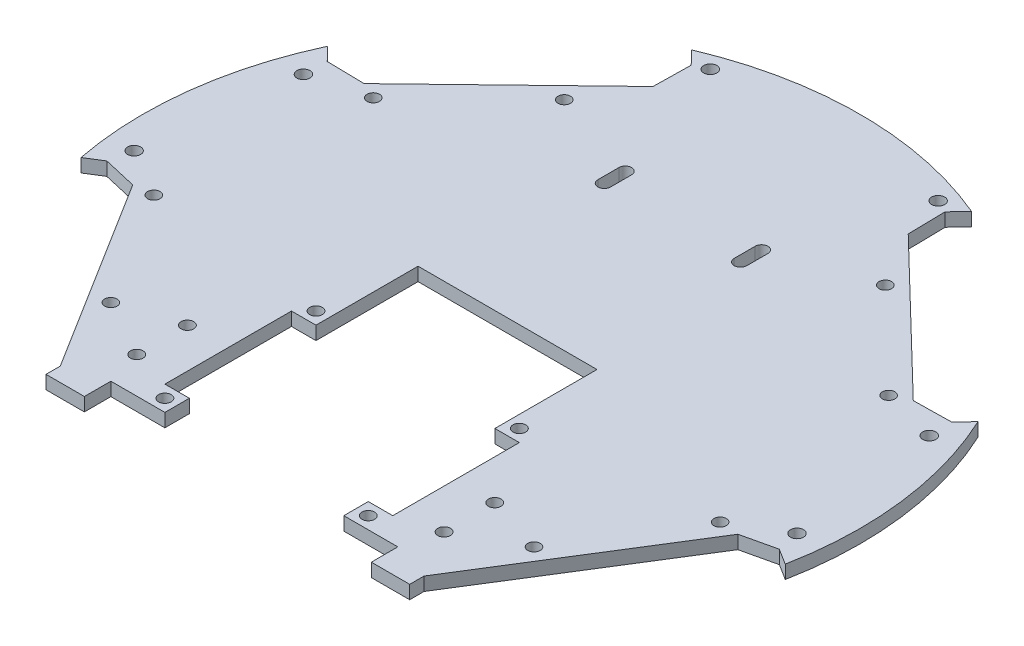
SolidWorks part; units mm, degrees
material "6061 Alloy"
ref_plane "Front Plane" through (0, 0, 0) normal (0, 0, 1) x (1, 0, 0)
ref_plane "Top Plane" through (0, 0, 0) normal (0, 1, 0) x (1, 0, 0)
ref_plane "Right Plane" through (0, 0, 0) normal (1, 0, 0) x (0, 0, -1)
sketch "Sketch1" plane through (0, 0, 0) normal (0, 1, 0) x (1, 0, 0)
  line L0 (0, 0) -> (0, -58.55) construction
  line L1 (-83.4462, -16.178) -> (-71.2857, -8.5793) construction
  line L6 (0, 0) -> (-59.046, 61.1439) construction
  line L7 (0, 0) -> (-72.0841, -45.0431) construction
  line L8 (-33.174, 78.2591) -> (-23.2129, 67.9442) construction
  line L9 (-72.0841, -45.0431) -> (-70.388, -43.9833) construction
  line L10 (-70.388, -43.9833) -> (-84.9608, -20.662) construction
  line L11 (-84.9608, -20.662) -> (-72.2401, -12.7132) construction
  line L12 (-72.2401, -12.7132) -> (-43.0945, -59.3558) construction
  line L13 (-43.0945, -59.3558) -> (-55.8152, -67.3046) construction
  line L14 (-55.8152, -67.3046) -> (-70.388, -43.9833) construction
  line L21 (-59.046, 61.1439) -> (-57.6566, 59.7052)
  line L22 (-77.4385, 40.6021) -> (-37.8748, 78.8083) construction
  line L23 (-73.9694, 32.6911) -> (-77.0537, 35.885)
  line L24 (-37.8748, 78.8083) -> (-27.4549, 68.0182) construction
  line L25 (-27.4549, 68.0182) -> (-67.0186, 29.812) construction
  line L26 (-67.0186, 29.812) -> (-77.4385, 40.6021) construction
  line L27 (-43.0945, -64.8266) -> (-34, -64.8266)
  line L33 (-86.5505, -18.1178) -> (-71.2857, -8.5793) construction
  line L34 (0, 0) -> (0, 50000) construction
  line L35 (0, 0) -> (-50000, 0) construction
  line L36 (-61.619, -58.55) -> (0, -58.55) construction
  line L38 (-67.0927, 25.57) -> (-79.5965, 38.5181) construction
  line L39 (-54.9774, -64.8266) -> (0, -64.8266) construction
  line L40 (-35.7168, 80.8923) -> (-23.2129, 67.9442) construction
  line L41 (-38.9606, -60.3102) -> (-54.2255, -69.8488) construction
  line L42 (-34, -58.55) -> (34, -58.55) construction
  line L43 (-43.0945, -64.8266) -> (-43.0945, -58.4123)
  line L45 (73.9694, 32.6911) -> (77.0537, 35.885)
  line L46 (-71.2857, -8.5793) -> (-38.9606, -60.3102) construction
  line L47 (83.4462, -16.178) -> (79.6809, -13.8252)
  line L48 (69.4846, -16.1792) -> (43.0945, -58.4123)
  line L49 (43.0945, -64.8266) -> (43.0945, -58.4123)
  line L50 (43.0945, -64.8266) -> (34, -64.8266)
  line L51 (34, -58.55) -> (34, -64.8266)
  line L52 (0, 0) -> (72.0841, -45.0431) construction
  line L53 (0, 0) -> (59.046, 61.1439) construction
  line L54 (-30.0897, 75.0653) -> (-30.2847, 63.8954)
  line L55 (-62.7996, 32.4961) -> (-30.2847, 63.8954)
  line L56 (-30.0897, 75.0653) -> (-33.174, 78.2591)
  line L57 (73.9694, 32.6911) -> (77.0537, 35.885)
  line L58 (30.0897, 75.0653) -> (33.174, 78.2591)
  line L59 (-34, -58.55) -> (-34, -53.55)
  line L60 (62.7996, 32.4961) -> (30.2847, 63.8954)
  line L61 (-73.9694, 32.6911) -> (-62.7996, 32.4961)
  line L62 (-77.0537, 35.885) -> (-67.0927, 25.57) construction
  line L63 (-83.4462, -16.178) -> (-79.6809, -13.8252)
  line L64 (-79.6809, -13.8252) -> (-69.4846, -16.1792)
  line L65 (-69.4846, -16.1792) -> (-43.0945, -58.4123)
  line L66 (-27.4549, 68.0182) -> (-23.2129, 67.9442) construction
  line L67 (-72.2401, -12.7132) -> (-71.2857, -8.5793) construction
  line L68 (30.0897, 75.0653) -> (30.2847, 63.8954)
  line L69 (73.9694, 32.6911) -> (62.7996, 32.4961)
  line L70 (-34, -58.55) -> (-34, -64.8266)
  line L71 (79.6809, -13.8252) -> (69.4846, -16.1792)
  line L72 (-34, -53.55) -> (-28, -53.55)
  line L73 (-28, -53.55) -> (-28, -58.55)
  line L74 (-28, -58.55) -> (28, -58.55)
  line L75 (28, -53.55) -> (28, -58.55)
  line L76 (34, -53.55) -> (28, -53.55)
  line L77 (34, -58.55) -> (34, -53.55)
  line L78 (-34, -58.55) -> (-28, -58.55)
  line L79 (28, -58.55) -> (34, -58.55)
  line L97 (-23.2129, 67.9442) -> (-67.0927, 25.57) construction
  circle A0 centre (0, 0) radius 85 construction
  circle A1 centre (0, 0) radius 90 construction
  arc A51 (-77.0537, 35.885) -> (-83.4462, -16.178) centre (0, 0) ccw
  arc A52 (77.0537, 35.885) -> (83.4462, -16.178) centre (0, 0) cw
  arc A54 (-33.174, 78.2591) -> (33.174, 78.2591) centre (0, 0) cw
  point P29 (-31.6318, 76.6622)
  point P33 (-47.2368, 48.9151)
  point P34 (31.6318, 76.6622)
  point P35 (-57.6673, -36.0345)
  point P85 (-57.6566, 59.7052)
  dimension "D2" = 58
  dimension "D12" = 170
  dimension "D14" = 34
  dimension "D15" = 3
  dimension "D3" = 180
  dimension "D4" = 64.8266
  dimension "D5" = 44
  dimension "D6" = 15
  dimension "D7" = 55
  dimension "D8" = 58.55
  dimension "D9" = 2
  dimension "D11" = 2
  dimension "D16" = 7
  dimension "D17" = 7
  dimension "D18" = 0.5
  dimension "D19" = 1
  dimension "D20" = 6
  dimension "D21" = 5
extrude "Boss-Extrude4" add sketch "Sketch1" along normal blind 3.175 contours A0 L70 | L59 L78 L73 L72 | L75 L79 L77 L76 region at (0, 0, -6.6852) region at (-31, 0, 56.05) region at (31, 0, 56.05)
ref_point "Rear_Axle_Center (L)"
ref_axis "Rear_Axle_Proj (L)" through (46.5421, 0, -48.1958) along (0, 1, 0)
ref_point "Front_Axle_Center (L)"
ref_axis "Front_Axle_Proj (L)" through (57.2432, 0, 35.7696) along (0, 1, 0)
ref_point "Front_Axle_Center (R)"
ref_axis "Front_Axle_Proj (R)" through (-57.2432, 0, 35.7696) along (0, 1, 0)
ref_point "Read_Axle_Center (R)"
ref_axis "Rear_Axle_Proj (R)" through (-46.5421, 0, -48.1958) along (0, 1, 0)
sketch "Sketch17" plane through (0, 3.175, 0) normal (0, 1, 0) x (1, 0, 0)
  line L0 (0, -53.55) -> (0, -58.55) construction
  line L1 (-34, -58.55) -> (34, -58.55) construction
  circle A0 centre (0, -53.55) radius 8.5
  dimension "D1" = 17
  dimension "D2" = 5
extrude "Boss-Extrude5" [suppressed] add sketch "Sketch17" against normal up to surface (3.175 mm away)
ref_plane "Plane1" through (0, 0, 10) normal (0, 0, 1) x (1, 0, 0)
hole_wizard "M3 Clearance Hole3" positions "Sketch18" profile "Sketch19" hole size "M3" standard "ANSI Metric" end condition through all
sketch "Sketch18" plane through (0, 0, 0) normal (0, -1, 0) x (-1, 0, 0)
  line L0 (-36.415, -50) -> (-36.415, -38) construction
  line L3 (0, 0) -> (0, -38) construction
  line L4 (36.415, -50) -> (36.415, -38) construction
  line L6 (0, -38) -> (36.415, -38) construction
  line L8 (0, -38) -> (-36.415, -38) construction
  point P1 (36.415, -50)
  point P3 (36.415, -38)
  point P5 (-36.415, -50)
  point P33 (-36.415, -38)
  dimension "D1" = 12
  dimension "D2" = 36.415
  dimension "D3" = 36.415
  dimension "D4" = 38
sketch "Sketch19" plane through (-36.415, 0, 50) normal (1, 0, 0) x (0, 0, -1)
  line L0 (0, 0) -> (0, 3.175)
  line L1 (0, 3.175) -> (1.5, 3.175)
  line L2 (1.5, 3.175) -> (1.5, 0)
  line L5 (1.5, 0) -> (0, 0)
  line L11 (0, -6.35) -> (0, 107.95) construction
  dimension "Thru Hole Dia." = 3
  dimension "Thru Hole Depth" = 3.175
hole_wizard "M3 Clearance Hole1" positions "Sketch11" profile "Sketch12" hole size "M3" standard "ANSI Metric" end condition through all
sketch "Sketch11" plane through (0, 3.175, 0) normal (0, 1, 0) x (1, 0, 0)
  line L0 (83.4462, -16.178) -> (79.6809, -13.8252) construction
  line L2 (73.9694, 32.6911) -> (77.0537, 35.885) construction
  line L4 (-73.9694, 32.6911) -> (-77.0537, 35.885) construction
  line L6 (0, 0) -> (0, -50000) construction
  line L7 (78.4111, 9.6277) -> (84.3664, 10.3589) construction
  line L10 (74.155, 27.2403) -> (78.5423, -8.4914) construction
  line L12 (78.4111, 9.6277) -> (76.3487, 9.3744) construction
  arc A7 (77.964, -12.7523) -> (72.563, 31.2347) centre (0, 0) ccw construction
  arc A13 (-77.964, -12.7523) -> (-72.563, 31.2347) centre (0, 0) cw construction
  arc A17 (83.4462, -16.178) -> (77.0537, 35.885) centre (0, 0) ccw construction
  point P34 (78.5423, -8.4914)
  point P66 (74.155, 27.2403)
  point P70 (-74.155, 27.2403)
  point P71 (-78.5423, -8.4914)
  dimension "D1" = 6
  dimension "D2" = 36
sketch "Sketch12" plane through (-78.5423, 3.175, 8.4914) normal (1, 0, 0) x (0, 0, 1)
  line L0 (0, 0) -> (0, 3.175)
  line L1 (0, 3.175) -> (1.55, 3.175)
  line L2 (1.55, 3.175) -> (1.55, 0)
  line L5 (1.55, 0) -> (0, 0)
  line L11 (0, -6.35) -> (0, 107.95) construction
  dimension "Thru Hole Dia." = 3.1
  dimension "Thru Hole Depth" = 3.175
hole_wizard "M3 Clearance Hole4" positions "Sketch9" profile "Sketch10" hole size "M3" standard "ANSI Metric" end condition through all
sketch "Sketch9" plane through (0, 0, 0) normal (0, -1, 0) x (-1, 0, 0)
  line L0 (0, 0) -> (0, 63.4318) construction
  line L1 (-38.0437, 52.9272) -> (38.0437, 52.9272) construction
  line L3 (61.0625, 30.6981) -> (-61.0625, 30.6981) construction
  line L4 (-67.0993, -15.2789) -> (67.0993, -15.2789) construction
  line L5 (50.1419, -42.4164) -> (-50.1419, -42.4164) construction
  line L6 (-61.0625, 30.6981) -> (-38.0437, 52.9272) construction
  line L7 (38.0437, 52.9272) -> (61.0625, 30.6981) construction
  line L8 (67.0993, -15.2789) -> (50.1419, -42.4164) construction
  line L9 (-50.1419, -42.4164) -> (-67.0993, -15.2789) construction
  line L10 (0, 0) -> (-44.8055, 46.3974) construction
  line L11 (0, 0) -> (44.8055, 46.3974) construction
  line L12 (0, 0) -> (-96.9468, 0) construction
  line L14 (-55.1231, -34.4448) -> (0, 0) construction
  line L15 (0, 0) -> (55.1231, -34.4448) construction
  line L18 (-69.4846, -16.1792) -> (-43.0945, -58.4123) construction
  line L19 (-62.7996, 32.4961) -> (-30.2847, 63.8954) construction
  point P0 (-67.0993, -15.2789)
  point P2 (-50.1419, -42.4164)
  point P9 (-61.0625, 30.6981)
  point P11 (-38.0437, 52.9272)
  point P30 (50.1419, -42.4164)
  point P31 (67.0993, -15.2789)
  point P32 (38.0437, 52.9272)
  point P33 (61.0625, 30.6981)
  dimension "D9" = 46
  dimension "D10" = 46
  dimension "D11" = 32
  dimension "D12" = 32
  dimension "D7" = 58
  dimension "D5" = 32
  dimension "D6" = 2.5
  dimension "D8" = 9.4
  dimension "D2" = 44
  dimension "D3" = 32
  dimension "D4" = 2.5
  dimension "D13" = 9.4
sketch "Sketch10" plane through (67.0993, 0, 15.2789) normal (1, 0, 0) x (0, 0, -1)
  line L0 (0, 0) -> (0, 3.175)
  line L1 (0, 3.175) -> (1.475, 3.175)
  line L2 (1.475, 3.175) -> (1.475, 0)
  line L5 (1.475, 0) -> (0, 0)
  line L11 (0, -6.35) -> (0, 107.95) construction
  dimension "Thru Hole Dia." = 2.95
  dimension "Thru Hole Depth" = 3.175
hole_wizard "M3 Clearance Hole2" positions "Sketch13" profile "Sketch14" hole size "M3" standard "ANSI Metric" end condition through all
sketch "Sketch13" plane through (0, 3.175, 0) normal (0, 1, 0) x (1, 0, 0)
  line L0 (0, 0) -> (0, 85) construction
  line L2 (-24, 47) -> (-24, 81) construction
  line L3 (-24, 47) -> (24, 47) construction
  line L4 (-24, 81) -> (24, 81) construction
  line L5 (24, 47) -> (24, 81) construction
  line L6 (-24, 47) -> (24, 81) construction
  line L7 (-24, 81) -> (24, 47) construction
  line L8 (-38.0437, 52.9272) -> (-61.0625, 30.6981) construction
  line L10 (-36.307, 51.1289) -> (-59.3259, 28.8998) construction
  line L11 (-16.3488, 39.8187) -> (-31.6313, 55.6441) construction
  line L12 (-16.3488, 39.8187) -> (-48.7191, 8.559) construction
  line L13 (-31.6313, 55.6441) -> (-64.0016, 24.3845) construction
  line L14 (-48.7191, 8.559) -> (-64.0016, 24.3845) construction
  line L15 (-16.3488, 39.8187) -> (-64.0016, 24.3845) construction
  line L16 (-31.6313, 55.6441) -> (-48.7191, 8.559) construction
  line L17 (-49.5531, 41.8127) -> (-40.1752, 32.1016) construction
  line L18 (-27, 76.4978) -> (-27, 80.5978) construction
  arc A0 (33.174, 78.2591) -> (-33.174, 78.2591) centre (0, 0) ccw construction
  circle A1 centre (-16.2162, 44) radius 3 construction
  circle A2 centre (-27, 76.4978) radius 3 construction
  point P65 (0, 64)
  point P181 (-27, 76.4978)
  point P184 (27, 76.4978)
  dimension "D7" = 6
  dimension "D1" = 48
  dimension "D2" = 34
  dimension "D3" = 4
  dimension "D5" = 45
  dimension "D6" = 22
  dimension "D8" = 4.1
  dimension "D4" = 2.5
sketch "Sketch14" plane through (27, 3.175, -76.4978) normal (1, 0, 0) x (0, 0, 1)
  line L0 (0, 0) -> (0, 3.175)
  line L1 (0, 3.175) -> (1.55, 3.175)
  line L2 (1.55, 3.175) -> (1.55, 0)
  line L5 (1.55, 0) -> (0, 0)
  line L11 (0, -6.35) -> (0, 107.95) construction
  dimension "Thru Hole Dia." = 3.1
  dimension "Thru Hole Depth" = 3.175
sketch "Sketch20" plane through (0, 3.175, 0) normal (0, 1, 0) x (1, 0, 0)
  line L0 (-16.1485, 45.5) -> (-16.1485, 40.5) construction
  line L1 (-14.6485, 45.5) -> (-14.6485, 40.5)
  line L2 (-17.6485, 45.5) -> (-17.6485, 40.5)
  line L3 (0, 0) -> (0, 85) construction
  line L5 (16.1485, 45.5) -> (16.1485, 40.5) construction
  line L6 (14.6485, 45.5) -> (14.6485, 40.5)
  line L7 (17.6485, 45.5) -> (17.6485, 40.5)
  arc A0 (-14.6485, 45.5) -> (-17.6485, 45.5) centre (-16.1485, 45.5) ccw
  arc A1 (-17.6485, 40.5) -> (-14.6485, 40.5) centre (-16.1485, 40.5) ccw
  arc A5 (33.174, 78.2591) -> (-33.174, 78.2591) centre (0, 0) ccw construction
  arc A7 (14.6485, 45.5) -> (17.6485, 45.5) centre (16.1485, 45.5) cw
  arc A8 (17.6485, 40.5) -> (14.6485, 40.5) centre (16.1485, 40.5) cw
  point P2 (-16.1485, 43)
  point P16 (16.1485, 43)
  dimension "D1" = 45.5
  dimension "D2" = 3
  dimension "D3" = 5
  dimension "D4" = 16.1485
extrude "Cut-Extrude1" cut sketch "Sketch20" against normal through all
sketch "Sketch22" plane through (0, 3.175, 0) normal (0, 1, 0) x (1, 0, 0)
  line L0 (-56.2896, -37.2958) -> (-57.6464, -38.1436) construction
  line L1 (-69.4846, -16.1792) -> (-43.0945, -58.4123) construction
  line L2 (-43.0945, -64.8266) -> (-43.0945, -58.4123) construction
  line L3 (30.2452, 66.1578) -> (65.062, 32.5356)
  line L4 (71.6894, -15.6702) -> (43.0945, -61.4316)
  line L28 (-30.2452, 66.1578) -> (-65.062, 32.5356)
  line L29 (-71.6894, -15.6702) -> (-43.0945, -61.4316)
  line L30 (-79.6809, -13.8252) -> (-69.4846, -16.1792) construction
  line L31 (0, 85) -> (0, -53.55) construction
  line L32 (-46.5421, 48.1958) -> (-47.6536, 49.3467) construction
  line L56 (-34, -58.55) -> (34, -58.55)
  line L60 (34, -58.55) -> (34, -64.8266)
  line L61 (34, -64.8266) -> (43.0945, -64.8266)
  line L62 (43.0945, -64.8266) -> (43.0945, -58.4123)
  line L63 (43.0945, -58.4123) -> (69.4846, -16.1792)
  line L64 (69.4846, -16.1792) -> (79.6809, -13.8252)
  line L65 (79.6809, -13.8252) -> (83.4462, -16.178)
  line L66 (77.0537, 35.885) -> (73.9694, 32.6911)
  line L67 (73.9694, 32.6911) -> (62.7996, 32.4961)
  line L68 (62.7996, 32.4961) -> (30.2847, 63.8954)
  line L69 (30.2847, 63.8954) -> (30.0897, 75.0653)
  line L70 (30.0897, 75.0653) -> (33.174, 78.2591)
  line L71 (-33.174, 78.2591) -> (-30.0897, 75.0653)
  line L72 (-30.0897, 75.0653) -> (-30.2847, 63.8954)
  line L73 (-30.2847, 63.8954) -> (-62.7996, 32.4961)
  line L74 (-62.7996, 32.4961) -> (-73.9694, 32.6911)
  line L75 (-73.9694, 32.6911) -> (-77.0537, 35.885)
  line L76 (-83.4462, -16.178) -> (-79.6809, -13.8252)
  line L77 (-79.6809, -13.8252) -> (-69.4846, -16.1792)
  line L78 (-69.4846, -16.1792) -> (-43.0945, -58.4123)
  line L79 (-43.0945, -58.4123) -> (-43.0945, -64.8266)
  line L80 (-43.0945, -64.8266) -> (-34, -64.8266)
  line L81 (-34, -64.8266) -> (-34, -58.55)
  line L84 (-34, -58.55) -> (34, -58.55)
  line L88 (34, -58.55) -> (34, -64.8266)
  line L89 (34, -64.8266) -> (43.0945, -64.8266)
  line L90 (43.0945, -64.8266) -> (43.0945, -58.4123)
  line L91 (43.0945, -58.4123) -> (69.4846, -16.1792)
  line L92 (69.4846, -16.1792) -> (79.6809, -13.8252)
  line L93 (79.6809, -13.8252) -> (83.4462, -16.178)
  line L94 (77.0537, 35.885) -> (73.9694, 32.6911)
  line L95 (73.9694, 32.6911) -> (62.7996, 32.4961)
  line L96 (62.7996, 32.4961) -> (30.2847, 63.8954)
  line L97 (30.2847, 63.8954) -> (30.0897, 75.0653)
  line L98 (30.0897, 75.0653) -> (33.174, 78.2591)
  line L99 (-33.174, 78.2591) -> (-30.0897, 75.0653)
  line L100 (-30.0897, 75.0653) -> (-30.2847, 63.8954)
  line L101 (-30.2847, 63.8954) -> (-62.7996, 32.4961)
  line L102 (-62.7996, 32.4961) -> (-73.9694, 32.6911)
  line L103 (-73.9694, 32.6911) -> (-77.0537, 35.885)
  line L104 (-83.4462, -16.178) -> (-79.6809, -13.8252)
  line L105 (-79.6809, -13.8252) -> (-69.4846, -16.1792)
  line L106 (-69.4846, -16.1792) -> (-43.0945, -58.4123)
  line L107 (-43.0945, -58.4123) -> (-43.0945, -64.8266)
  line L108 (-43.0945, -64.8266) -> (-34, -64.8266)
  line L109 (-34, -64.8266) -> (-34, -58.55)
  arc A9 (83.4462, -16.178) -> (77.0537, 35.885) centre (0, 0) ccw
  arc A10 (33.174, 78.2591) -> (-33.174, 78.2591) centre (0, 0) ccw
  arc A11 (-77.0537, 35.885) -> (-83.4462, -16.178) centre (0, 0) ccw
  arc A13 (83.4462, -16.178) -> (77.0537, 35.885) centre (0, 0) ccw
  arc A14 (33.174, 78.2591) -> (-33.174, 78.2591) centre (0, 0) ccw
  arc A15 (-77.0537, 35.885) -> (-83.4462, -16.178) centre (0, 0) ccw
  dimension "D2" = 1.6
  dimension "D1" = 0
extrude "Boss-Extrude6" add sketch "Sketch22" against normal up to surface (3.175 mm away) contours L102 L101 L100 L28 | L107 L106 L105 L29 | L92 L91 L90 L4 | L97 L96 L95 L3 region at (47.1042, 3.175, -48.7778) region at (-47.1042, 3.175, -48.7778) region at (56.8481, 3.175, 37.9317) region at (-56.8481, 3.175, 37.9317) up to face at (-16.1485, 0, -43)
fillet "Fillet1" [suppressed] radius 2
fillet "Fillet3" [suppressed] radius 1
sketch "Sketch23" [suppressed] plane through (0, 3.175, 0) normal (0, 1, 0) x (1, 0, 0)
  circle A0 centre (0, -53.55) radius 4.95
  dimension "D1" = 9.9
extrude "Cut-Extrude2" [suppressed] cut sketch "Sketch23" against normal through all
sketch "Sketch24" plane through (0, 3.175, 0) normal (0, 1, 0) x (1, 0, 0)
  line L0 (0, -58.55) -> (0, 85) construction
  line L1 (-34, -58.55) -> (34, -58.55) construction
  line L2 (-27, -52.75) -> (-27, -22.75)
  line L5 (0, 1.45) -> (-21.2, 1.45)
  line L9 (0, 1.45) -> (21.2, 1.45)
  line L11 (-27, -22.75) -> (-21.2, -22.75)
  line L13 (-21.2, -58.55) -> (-21.2, -52.75)
  line L14 (-21.2, -52.75) -> (-27, -52.75)
  line L17 (21.2, -58.55) -> (21.2, -52.75)
  line L18 (21.2, -52.75) -> (27, -52.75)
  line L20 (27, -52.75) -> (27, -22.75)
  line L21 (27, -22.75) -> (21.2, -22.75)
  line L22 (-21.2, -22.75) -> (-21.2, 1.45)
  line L23 (21.2, -58.55) -> (-21.2, -58.55)
  line L24 (21.2, -22.75) -> (21.2, 1.45)
  arc A0 (33.174, 78.2591) -> (-33.174, 78.2591) centre (0, 0) ccw construction
  point P16 (0, 0)
  point P17 (0, 0)
  point P23 (0, -58.55)
  dimension "D1" = 42.4
  dimension "D2" = 5.8
  dimension "D3" = 60
  dimension "D4" = 5.8
  dimension "D5" = 5.8
  dimension "D6" = 5.8
  dimension "D7" = 5.8
  dimension "D8" = 30
  dimension "D9" = 30
  dimension "D10" = 5.8
extrude "Cut-Extrude3" cut sketch "Sketch24" against normal through all
sketch "Sketch25" plane through (0, 3.175, 0) normal (0, 1, 0) x (1, 0, 0)
  line L0 (-21.2, -55.65) -> (-24.1, -55.65) construction
  line L1 (-21.2, -52.75) -> (-21.2, -58.55) construction
  line L2 (-24.1, -22.75) -> (-24.1, -19.85) construction
  line L4 (-21.2, -22.75) -> (-27, -22.75) construction
  line L5 (24.1, -22.75) -> (24.1, -19.85) construction
  line L6 (27, -22.75) -> (21.2, -22.75) construction
  line L7 (21.2, -55.65) -> (24.1, -55.65) construction
  line L8 (21.2, -58.55) -> (21.2, -52.75) construction
  circle A1 centre (-24.1, -55.65) radius 1.5
  circle A2 centre (-24.1, -19.85) radius 1.5
  circle A3 centre (24.1, -19.85) radius 1.5
  circle A4 centre (24.1, -55.65) radius 1.5
  dimension "D2" = 3
  dimension "D4" = 3
  dimension "D6" = 3
  dimension "D8" = 3
  dimension "D1" = 2.9
  dimension "D3" = 2.9
  dimension "D5" = 2.9
  dimension "D7" = 2.9
extrude "Cut-Extrude4" cut sketch "Sketch25" against normal through all
equation "\"D3@Sketch18\"=\"D2@Sketch18\""
equation "\"D2@Sketch18\"=72.83/2"
equation "\"D3@Sketch9\"=\"D5@Sketch9\""
equation "\"D4@Sketch9\"=\"D6@Sketch9\""
equation "\"D13@Sketch9\"=\"D8@Sketch9\""
